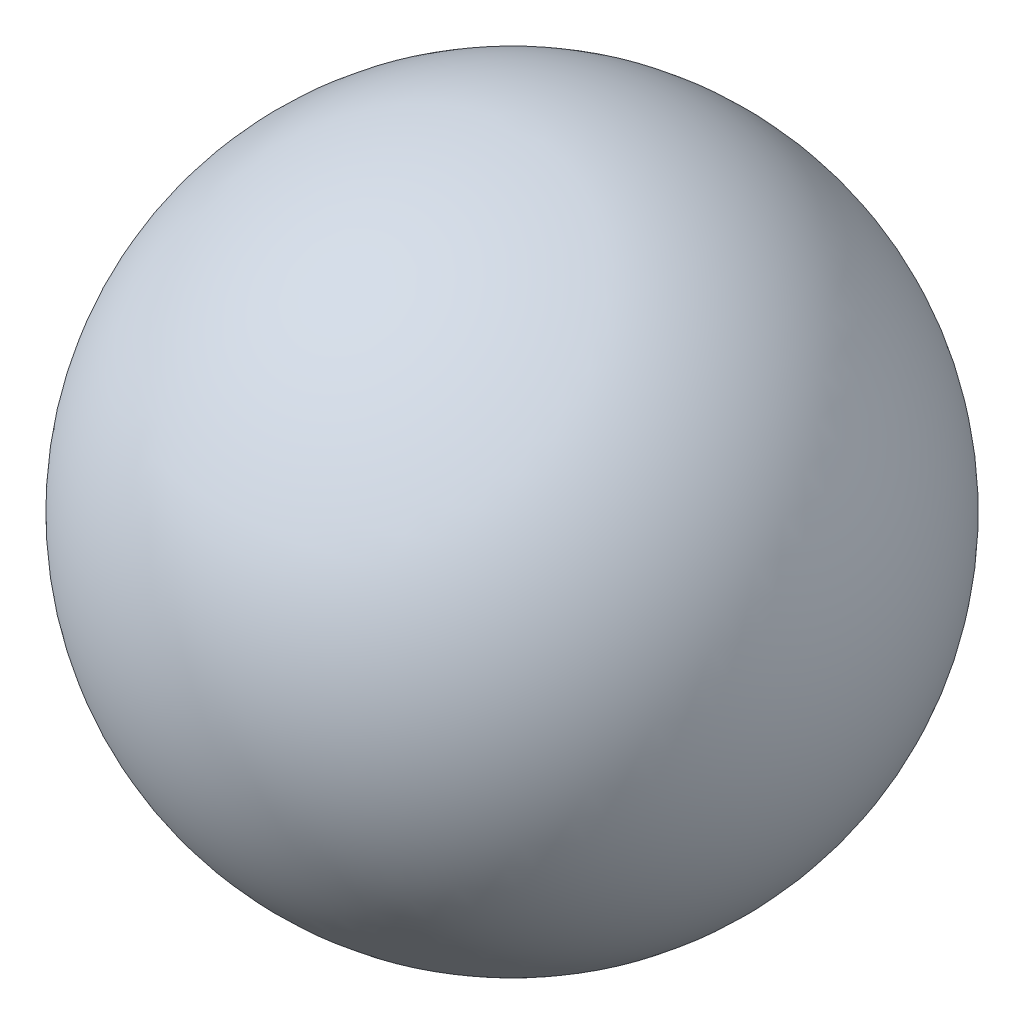
SolidWorks part; units mm, degrees
ref_plane "Front Plane" through (0, 0, 0) normal (0, 0, 1) x (1, 0, 0)
ref_plane "Top Plane" through (0, 0, 0) normal (0, 1, 0) x (1, 0, 0)
ref_plane "Right Plane" through (0, 0, 0) normal (1, 0, 0) x (0, 0, -1)
sketch "Sketch1" plane through (0, 0, 0) normal (0, 0, 1) x (1, 0, 0)
  line L0 (0, 11) -> (0, -11)
  arc A0 (0, 11) -> (0, -11) centre (0, 0) ccw
  dimension "D1" = 22
revolve "Revolve2" add sketch "Sketch1" angle 360 about L0
ref_axis "Axis1" through (0, 11, 0) along (0, -1, 0)
